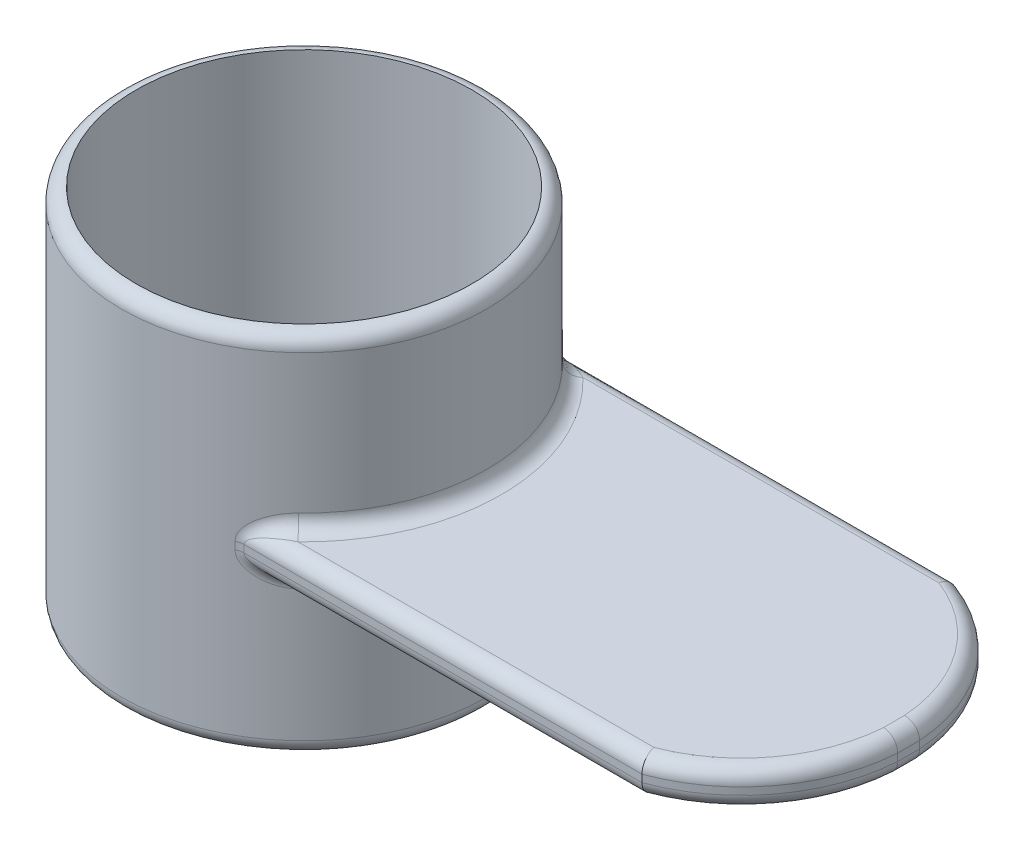
SolidWorks part; units mm, degrees
ref_plane "Front Plane" through (0, 0, 0) normal (0, 0, 1) x (1, 0, 0)
ref_plane "Top Plane" through (0, 0, 0) normal (0, 1, 0) x (1, 0, 0)
ref_plane "Right Plane" through (0, 0, 0) normal (1, 0, 0) x (0, 0, -1)
sketch "Base" plane through (0, 0, 0) normal (0, 1, 0) x (1, 0, 0)
  line L0 (82.7574, 21.5) -> (82.7574, -21.5)
  line L1 (82.7574, 21.5) -> (12.7574, 21.5)
  line L4 (12.7574, -21.5) -> (82.7574, -21.5)
  circle A0 centre (0, 0) radius 25
  point P4 (12.3935, 21.711)
  point P6 (85.0624, -21.473)
  dimension "D1" = 50
  dimension "D2" = 43
  dimension "D3" = 70
  dimension "D4" = 70
extrude "Boss-Extrude3" add sketch "Base" along normal blind 50 contours A0 L4 region at (0, 0, 0)
extrude "Boss-Extrude4" add sketch "Base<4>" along normal blind 27 contours A0 L4 L0 L1 region at (51.9953, 0, 0)
sketch "Base<4>" plane through (0, 0, 0) normal (0, 1, 0) x (1, 0, 0) same geometry as "Base"
extrude "Cut-Extrude4" cut sketch "Base<5>" along normal blind 22 contours A0 L4 L0 L1 region at (51.9953, 0, 0)
sketch "Base<5>" plane through (0, 0, 0) normal (0, 1, 0) x (1, 0, 0) same geometry as "Base"
sketch "Sketch3" plane through (0, 50, 0) normal (0, 1, 0) x (1, 0, 0)
  circle A0 centre (0, 0) radius 23
  point P3 (0, 0)
  dimension "D1" = 46
extrude "Cut-Extrude5" cut sketch "Sketch3" against normal blind 47
sketch "Sketch5" plane through (0, 22, 0) normal (0, -1, 0) x (1, 0, 0)
  line L1 (12.7574, 21.5) -> (82.7574, 21.5) construction
  line L2 (82.7574, -21.5) -> (12.7574, -21.5) construction
  arc A0 (67.7574, 21.5) -> (67.7574, -21.5) centre (59.9241, 0) cw
  point P0 (66.8296, -21.5)
  point P1 (82.8066, 0)
  dimension "D1" = 15
  dimension "D2" = 15
extrude "Cut-Extrude6" cut sketch "Sketch5" against normal through all and the other way through all
fillet "Fillet1" radius 2 16 edges at (25, 27, 0) (12.7574, 24.5, -21.5) (12.7574, 24.5, 21.5) (82.7574, 22, 0) (78.2297, 22, -13.7301) (40.2574, 22, -21.5) (25, 22, 0) (40.2574, 22, 21.5) (78.2297, 22, 13.7301) (40.2574, 27, -21.5) (82.7574, 27, 0) (78.2297, 27, -13.7301) (78.2297, 27, 13.7301) (40.2574, 27, 21.5) (0, 50, 25) (0, 0, 25)
